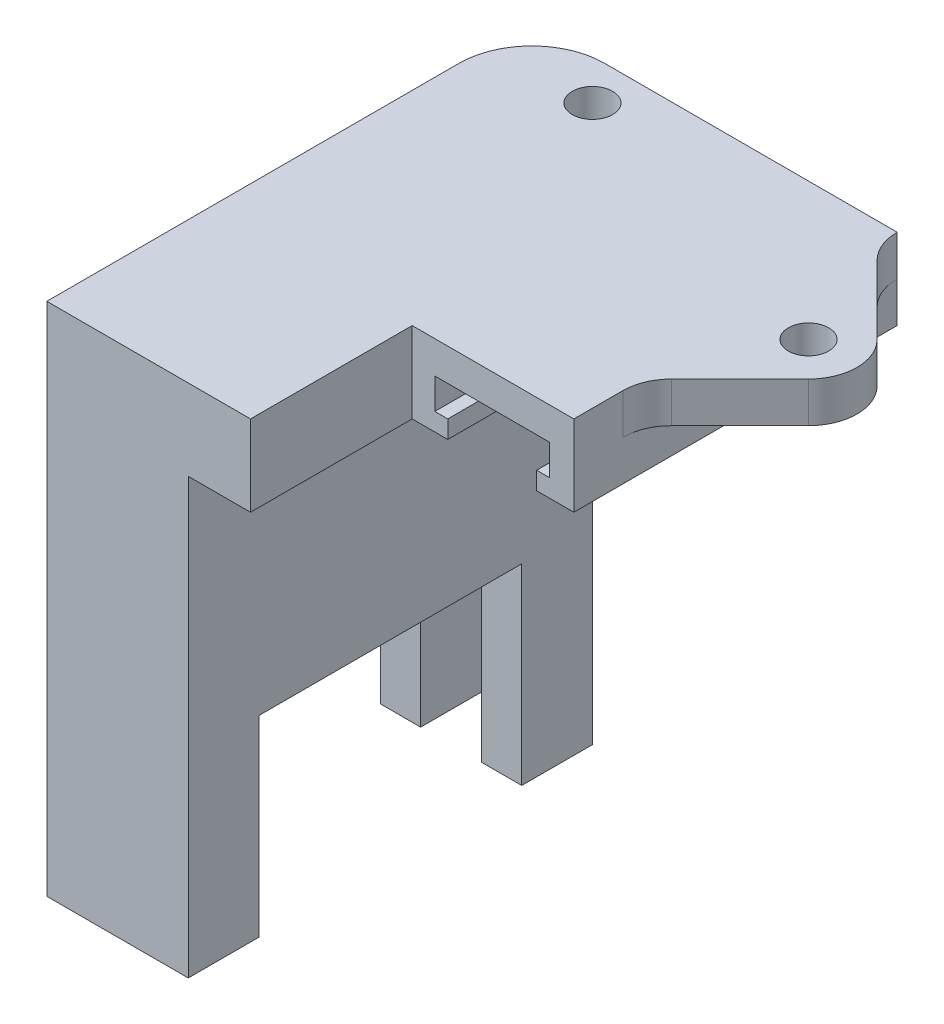
SolidWorks part; units mm, degrees
ref_plane "Front Plane" through (0, 0, 0) normal (0, 0, 1) x (1, 0, 0)
ref_plane "Top Plane" through (0, 0, 0) normal (0, 1, 0) x (1, 0, 0)
ref_plane "Right Plane" through (0, 0, 0) normal (1, 0, 0) x (0, 0, -1)
sketch "Sketch1" plane through (0, 0, 0) normal (0, 0, 1) x (1, 0, 0)
  line L0 (-12.827, 0) -> (12.827, 0)
  line L1 (12.827, 0) -> (12.827, -12.7)
  line L2 (12.827, -12.7) -> (6.985, -12.7)
  line L3 (6.985, -12.7) -> (6.985, -9.906)
  line L4 (6.985, -9.906) -> (9.017, -9.906)
  line L5 (9.017, -9.906) -> (9.017, -5.08)
  line L6 (9.017, -5.08) -> (-9.017, -5.08)
  line L7 (0, 0) -> (0, -5.08) construction
  line L8 (-9.017, -9.906) -> (-9.017, -5.08)
  line L9 (-6.985, -9.906) -> (-9.017, -9.906)
  line L10 (-6.985, -12.7) -> (-6.985, -9.906)
  line L11 (-12.827, -12.7) -> (-6.985, -12.7)
  line L12 (-12.827, 0) -> (-12.827, -12.7)
  dimension "D1" = 2.794
  dimension "D2" = 13.97
  dimension "D3" = 18.034
  dimension "D4" = 7.62
  dimension "D5" = 12.7
  dimension "D6" = 3.81
extrude "Boss-Extrude1" add sketch "Sketch1" along normal mid plane 76.2
sketch "Sketch3" plane through (0, 0, 0) normal (0, 1, 0) x (1, 0, 0)
  line L0 (12.827, 16.5474) -> (28.067, 16.5474) construction
  line L1 (12.827, -38.1) -> (12.827, 38.1) construction
  line L2 (0, 38.1) -> (0, -38.1) construction
  line L3 (12.827, 38.1) -> (-12.827, 38.1) construction
  line L4 (12.827, -38.1) -> (-12.827, -38.1) construction
  line L5 (15.0588, 32.7118) -> (25.8352, 21.9355)
  line L6 (12.827, 38.1) -> (12.827, -5.0052)
  line L8 (12.827, -5.0052) -> (12.827, -38.1) construction
  line L9 (15.0588, 0.3829) -> (25.8352, 11.1592)
  arc A0 (25.8352, 11.1592) -> (25.8352, 21.9355) centre (20.447, 16.5474) ccw
  arc A1 (15.0588, 32.7118) -> (12.827, 38.1) centre (20.447, 38.1) cw
  circle A2 centre (20.447, 16.5474) radius 3.175
  arc A3 (15.0588, 0.3829) -> (12.827, -5.0052) centre (20.447, -5.0052) ccw
  point P4 (0, 0)
  point P12 (0, 0)
  point P15 (12.827, 38.1)
  point P19 (0, 0)
  point P20 (0, 0)
  point P27 (0, 0)
  point P28 (0, 0)
  point P29 (12.827, 34.0236)
  point P30 (0, 0)
  point P31 (0, 0)
  point P33 (0, 0)
  point P34 (12.827, -38.1)
  line M9 (-12.827, 38.1) -> (-12.827, -38.1)
  line M11 (12.827, -38.1) -> (12.827, 38.1)
  dimension "D1" = 7.62
  dimension "D2" = 6.35
  dimension "D3" = 7.62
  dimension "D4" = 7.62
  dimension "D5" = 45
extrude "Boss-Extrude3" add sketch "Sketch3" against normal blind 6.35 contours A3 L9 A0 L5 A1 A2 M11 | M9 region at (20.1237, 0, -27.0004)
sketch "Sketch4" plane through (0, 0, 38.1) normal (0, 0, 1) x (1, 0, 0)
  line L0 (-12.827, 0) -> (-44.577, 0)
  line L1 (-44.577, 0) -> (-44.577, -50.8)
  line L2 (-44.577, -50.8) -> (-22.352, -50.8)
  line L3 (-22.352, -50.8) -> (-22.352, -12.7)
  line L4 (-22.352, -12.7) -> (-12.827, -12.7)
  line L5 (-12.827, 0) -> (-12.827, -12.7)
  dimension "D1" = 50.8
  dimension "D2" = 9.525
  dimension "D3" = 31.75
extrude "Boss-Extrude4" add sketch "Sketch4" against normal blind 63.5
sketch "Sketch5" plane through (-44.577, 0, 0) normal (-1, 0, 0) x (0, 0, 1)
  line L1 (-25.4, -50.8) -> (-14.2875, -50.8)
  line L2 (-25.4, -50.8) -> (-25.4, -80.9625)
  line L3 (-25.4, -80.9625) -> (-14.2875, -80.9625)
  line L4 (-14.2875, -50.8) -> (-14.2875, -80.9625)
  line L5 (38.1, -50.8) -> (26.9875, -50.8)
  line L6 (38.1, -50.8) -> (38.1, -80.9625)
  line L7 (38.1, -80.9625) -> (26.9875, -80.9625)
  line L8 (26.9875, -50.8) -> (26.9875, -80.9625)
  dimension "D1" = 41.275
  dimension "D2" = 30.1625
extrude "Boss-Extrude5" add sketch "Sketch5" against normal up to surface (22.225 mm away) up to face at (-22.352, -31.75, 6.35)
sketch "Sketch7" plane through (0, 0, -25.4) normal (0, 0, -1) x (-1, 0, 0)
  line L0 (22.352, -50.8) -> (44.577, -50.8) construction
  line L1 (22.352, -50.8) -> (44.577, -50.8) construction
  line L2 (22.352, -80.9625) -> (44.577, -80.9625) construction
  line L3 (38.227, -50.8) -> (28.702, -50.8)
  line L4 (38.227, -50.8) -> (38.227, -80.9625)
  line L5 (38.227, -80.9625) -> (28.702, -80.9625)
  line L6 (28.702, -50.8) -> (28.702, -80.9625)
  line L7 (33.4645, -50.8) -> (33.4645, -80.9625) construction
  dimension "D1" = 9.525
extrude "Cut-Extrude1" cut sketch "Sketch7" against normal up to next
sketch "Sketch8" plane through (0, 0, 0) normal (0, 1, 0) x (1, 0, 0)
  line L0 (-28.702, 38.1) -> (-28.702, 25.4) construction
  line L1 (-44.577, 25.4) -> (-12.827, 25.4)
  line L2 (-44.577, 25.4) -> (-44.577, 38.1)
  line L3 (-44.577, 38.1) -> (-12.827, 38.1)
  line L4 (-12.827, 25.4) -> (-12.827, 38.1)
  circle A0 centre (-28.702, 31.75) radius 3.175
  dimension "D1" = 6.35
extrude "Boss-Extrude6" add sketch "Sketch8" against normal blind 6.35
fillet "Fillet1" radius 11.43 1 edges at (-44.577, -3.175, -38.1)
sketch "Sketch9" plane through (0, -12.7, 0) normal (0, -1, 0) x (-1, 0, 0)
  line L1 (-12.827, -38.1) -> (12.573, -38.1)
  line L2 (-12.827, -38.1) -> (-12.827, -12.7)
  line L3 (-12.827, -12.7) -> (12.573, -12.7)
  line L4 (12.573, -38.1) -> (12.573, -12.7)
  dimension "D1" = 25.4
  dimension "D2" = 25.4
extrude "Cut-Extrude2" cut sketch "Sketch9" against normal up to next contours L2 L3 L4 L1
sketch "Sketch2" plane through (0, 0, 0) normal (1, 0, 0) x (0, 0, -1)
  line L0 (-12.7, -5.08) -> (38.1, -5.08) construction
  line L1 (-12.7, -5.08) -> (38.1, -5.08) construction
  line L2 (32.258, -5.08) -> (34.798, -8.89)
  line L3 (34.798, -8.89) -> (37.338, -5.08)
  line L4 (37.338, -5.08) -> (32.258, -5.08)
  line L5 (34.798, -8.89) -> (34.798, -5.08) construction
  dimension "D1" = 3.81
  dimension "D2" = 5.08
  dimension "D3" = 47.498
extrude "Boss-Extrude2" add sketch "Sketch2" along normal mid plane 2.54 contours L3 L4 L2
